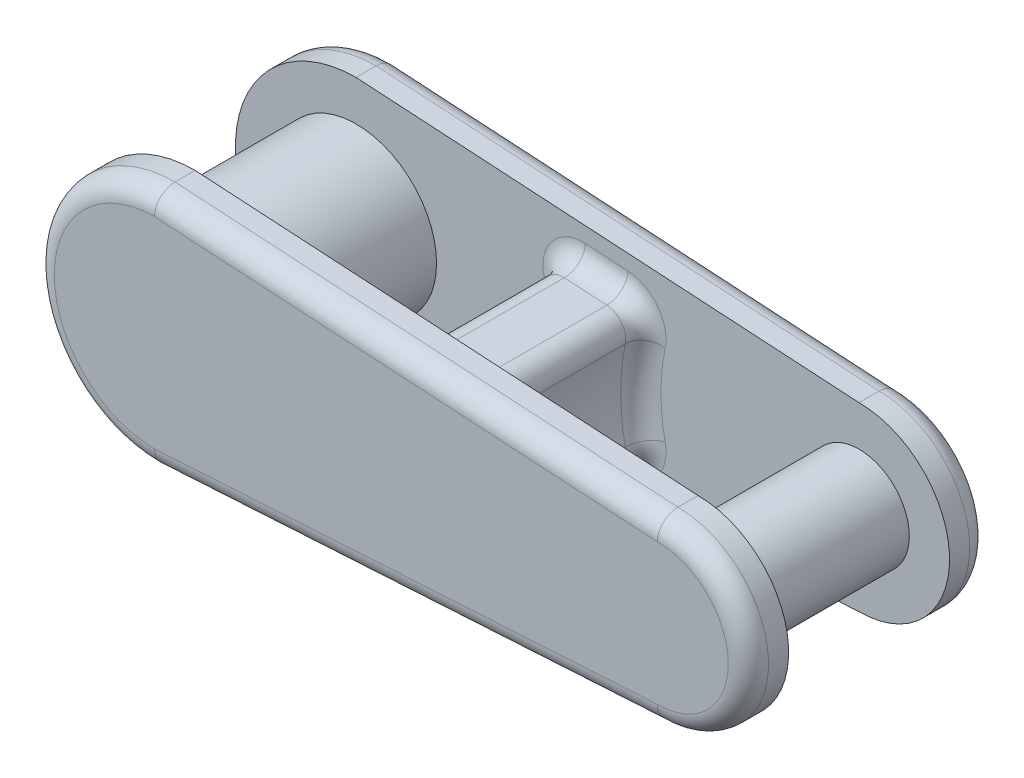
SolidWorks part; units mm, degrees
ref_plane "Front Plane" through (0, 0, 0) normal (0, 0, 1) x (1, 0, 0)
ref_plane "Top Plane" through (0, 0, 0) normal (0, 1, 0) x (1, 0, 0)
ref_plane "Right Plane" through (0, 0, 0) normal (1, 0, 0) x (0, 0, -1)
sketch "Sketch1" plane through (0, 0, 0) normal (0, 0, 1) x (1, 0, 0)
  circle A0 centre (0, 0) radius 40
  circle A1 centre (250, 0) radius 25
  dimension "D1" = 80
  dimension "D2" = 50
  dimension "D3" = 250
extrude "Boss-Extrude1" add sketch "Sketch1" along normal mid plane 80
sketch "Sketch2" plane through (0, 0, 40) normal (0, 0, 1) x (1, 0, 0)
  line L0 (250, -45) -> (0, -60)
  line L1 (0, 60) -> (250, 45)
  circle A0 centre (0, 0) radius 60
  circle A1 centre (250, 0) radius 45
  circle M2 centre (0, 0) radius 40
  dimension "D1" = 120
  dimension "D2" = 90
extrude "Boss-Extrude2" add sketch "Sketch2" along normal blind 20 contours A1 L1 A0 L0 | L1 A0 L0 M2 | A1 | M2 region at (128.9979, 0, 40) region at (250, 0, 40) region at (3.4854, -58.0908, 40) region at (0, 0, 40)
sketch "Sketch3" plane through (0, 0, 40) normal (0, 0, -1) x (-1, 0, 0)
  line L0 (-146.8363, 33.5314) -> (-99.281, 36.3847)
  line L1 (0, 60) -> (-250, 45) construction
  line L2 (-250, 0) -> (0, 0) construction
  line L3 (-146.8363, -33.5314) -> (-99.281, -36.3847)
  arc A0 (-146.8363, -33.5314) -> (-146.8363, 33.5314) centre (-250, 0) ccw
  arc A1 (-99.281, 36.3847) -> (-99.281, -36.3847) centre (0, 0) ccw
extrude "Boss-Extrude3" add sketch "Sketch3" along normal blind 80
sketch3d "3DSketch1"
  line L0 (249.7191, -34.9989, 60) -> (-0.2861, -49.9992, 60)
  line L1 (-0.2861, 49.9992, 60) -> (249.7191, 34.9989, 60)
  line L2 (249.7191, -34.9989, 60) -> (-0.2861, -49.9992, 60)
  line L3 (-0.2861, 49.9992, 60) -> (249.7191, 34.9989, 60)
  arc A0 (249.7191, -34.9989, 60) -> (249.7191, 34.9989, 60) centre (250, 0, 60) ccw
  arc A1 (-0.2861, 49.9992, 60) -> (-0.2861, -49.9992, 60) centre (0, 0, 60) ccw
  arc A2 (249.7191, -34.9989, 60) -> (249.7191, 34.9989, 60) centre (250, 0, 60) ccw
  arc A3 (-0.2861, 49.9992, 60) -> (-0.2861, -49.9992, 60) centre (0, 0, 60) ccw
  point P4 (250, 0, 95)
  point P7 (0, 0, 110)
  point P8 (250, 0, 95)
  point P9 (0, 0, 110)
  dimension "D1" = 10
mirror "Mirror1" about plane through (0, 0, 0) normal (0, 0, 1) of "Boss-Extrude2"
fillet "Fillet1" radius 10 8 edges at (295, 0, -60) (125, 52.5, -60) (-60, 0, -60) (125, -52.5, -60) (-60, 0, 60) (125, 52.5, 60) (295, 0, 60) (125, -52.5, 60)
fillet "Fillet2" radius 10 12 edges at (105.7382, 0, -40) (105.7382, 0, 40) (141.5237, 0, -40) (141.5237, 0, 40) (146.8363, -33.5314, 0) (123.0587, -34.9581, -40) (99.281, -36.3847, 0) (123.0587, -34.9581, 40) (99.281, 36.3847, 0) (123.0587, 34.9581, -40) (146.8363, 33.5314, 0) (123.0587, 34.9581, 40)
